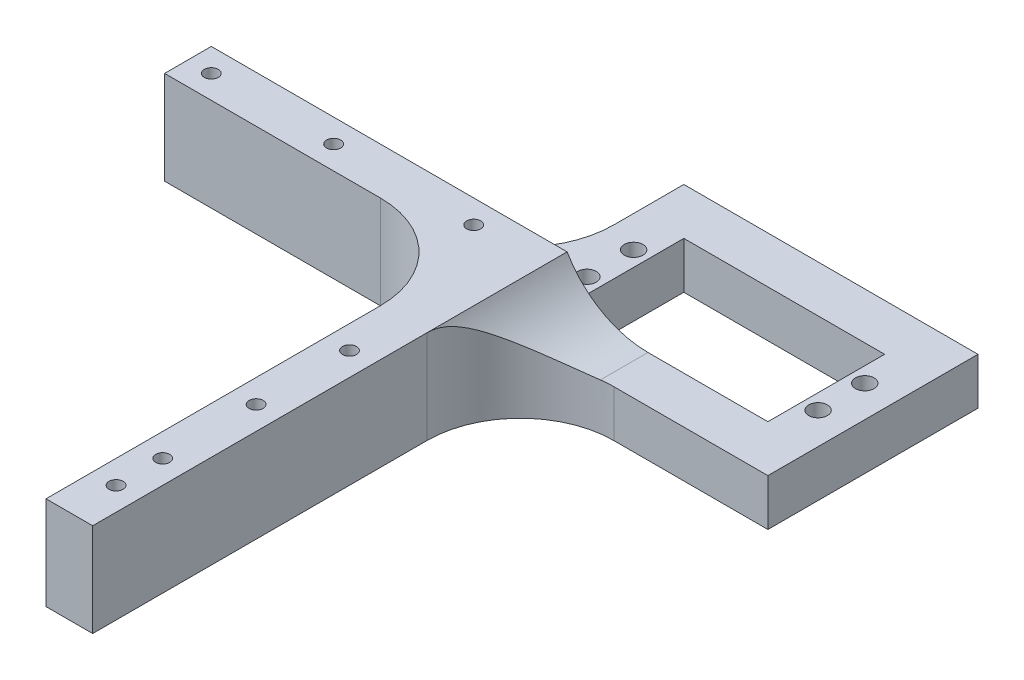
SolidWorks part; units mm, degrees
ref_plane "Front" through (0, 0, 0) normal (0, 0, 1) x (1, 0, 0)
ref_plane "Top" through (0, 0, 0) normal (0, 1, 0) x (1, 0, 0)
ref_plane "Right" through (0, 0, 0) normal (1, 0, 0) x (0, 0, -1)
sketch "Sketch1" plane through (0, 0, 0) normal (0, 1, 0) x (1, 0, 0)
  line L0 (0, 5) -> (0, -5)
  line L1 (-21.5, 12.5) -> (21.5, 12.5)
  line L2 (-21.5, 12.5) -> (-21.5, -12.5)
  line L3 (-21.5, -12.5) -> (21.5, -12.5)
  line L4 (21.5, 12.5) -> (21.5, -12.5)
  line L5 (-21.5, 12.5) -> (21.5, -12.5) construction
  line L6 (-21.5, -12.5) -> (21.5, 12.5) construction
  line L7 (-31.5, 22.5) -> (31.5, 22.5)
  line L8 (-31.5, 22.5) -> (-31.5, -22.5)
  line L9 (-31.5, -22.5) -> (31.5, -22.5)
  line L10 (31.5, 22.5) -> (31.5, -22.5)
  line L11 (-31.5, 22.5) -> (31.5, -22.5) construction
  line L12 (-31.5, -22.5) -> (31.5, 22.5) construction
  line L13 (-24.75, 5) -> (24.75, 5)
  line L14 (-24.75, -5) -> (24.75, -5)
  circle A0 centre (-24.75, 5) radius 2
  circle A1 centre (-24.75, -5) radius 2
  circle A2 centre (24.75, 5) radius 2
  circle A3 centre (24.75, -5) radius 2
  point P0 (0, 0)
  point P6 (0, 0)
  point P14 (0, 0)
  point P17 (0, 5)
  point P20 (0, -5)
  dimension "D1" = 43
  dimension "D2" = 25
  dimension "D3" = 10
  dimension "D4" = 10
  dimension "D5" = 10
  dimension "D6" = 49.5
extrude "Boss-Extrude1" add sketch "Sketch1" along normal blind 10 contours L10 L7 L8 L9 A3 L4 L3 L2 A1 A0 L1 A2 region at (0, 0, -21.7258)
sketch "Sketch2" plane through (-31.5, 0, 0) normal (-1, 0, 0) x (0, 0, 1)
  line L0 (-22.5, 0) -> (22.5, 0) construction
  line L1 (22.5, 10) -> (12.5, 10)
  line L3 (22.5, 0) -> (12.5, 0)
  line L5 (12.5, 0) -> (12.5, 20)
  line L6 (12.5, 20) -> (22.5, 20)
  line L7 (22.5, 10) -> (22.5, 0) construction
  line L8 (22.5, 20) -> (22.5, 0)
  line M3 (-22.5, 0) -> (22.5, 0)
  line M4 (22.5, 0) -> (22.5, 10)
  line M5 (22.5, 10) -> (-22.5, 10)
  dimension "D1" = 10
  dimension "D2" = 10
  dimension "D3" = 20
extrude "Boss-Extrude2" add sketch "Sketch2" along normal blind 76.2 contours L6 L5 M3 M4 | L8 L6 L5 M5 region at (-31.5, 5, 17.5) region at (-31.5, 15, 17.5)
sketch "Sketch3" plane through (0, 0, 22.5) normal (0, 0, 1) x (1, 0, 0)
  line L0 (-107.7, 0) -> (31.5, 0) construction
  line L1 (-21.5, 10) -> (-31.5, 10)
  line L2 (-21.5, 10) -> (-21.5, 0)
  line L3 (-21.5, 0) -> (-31.5, 0)
  line L4 (-31.5, 10) -> (-31.5, 0)
  line L5 (-107.7, 0) -> (-107.7, 20) construction
  point P7 (0, 0)
  dimension "D1" = 10
  dimension "D2" = 76.2
  dimension "D3" = 10
extrude "Boss-Extrude3" add sketch "Sketch3" along normal blind 91.6
sketch "Sketch5" plane through (0, 10, 0) normal (0, 1, 0) x (1, 0, 0)
  line L0 (-31.5, -12.5) -> (-21.5, -12.5)
  line L1 (-21.5, -12.5) -> (-21.5, -114.1)
  line L2 (-21.5, -114.1) -> (-31.5, -114.1)
  line L3 (-31.5, -114.1) -> (-31.5, -12.5)
extrude "Boss-Extrude4" add sketch "Sketch5" along normal blind 10
sketch "Sketch4" plane through (0, 10, 0) normal (0, 1, 0) x (1, 0, 0)
  line L0 (-107.7, -17.5) -> (-66.5, -17.5)
  line L1 (-107.7, -22.5) -> (-107.7, -12.5) construction
  line L2 (-66.5, -17.5) -> (-36.5, -17.5)
  circle A0 centre (-92.7, -17.5) radius 1.5
  circle A1 centre (-66.5, -17.5) radius 1.5
  circle A2 centre (-36.5, -17.5) radius 1.5
  dimension "D1" = 41.2
  dimension "D2" = 30
  dimension "D3" = 15
extrude "Cut-Extrude1" cut sketch "Sketch4" against normal through all and the other way through all contours L0 A0 | L0 A0 | A1 | A2 region at (-92.7, 10, 16.8634) region at (-92.7, 10, 18.1366)
fillet "Fillet5" radius 20 2 edges at (-31.5, 5, 12.5) (-31.5, 10, 22.5)
fillet "Fillet7" radius 20 1 edges at (-21.5, 10, 17.5)
fillet "Fillet8" radius 3 1 edges at (-36.5, 10, 12.5)
fillet "Fillet9" radius 20 1 edges at (-21.5, 10, 22.5)
sketch "Sketch6" plane through (-107.7, 0, 0) normal (-1, 0, 0) x (0, 0, 1)
  line L1 (12.5, 0) -> (22.5, 0)
  line L2 (12.5, 0) -> (12.5, 20)
  line L3 (12.5, 20) -> (22.5, 20)
  line L4 (22.5, 0) -> (22.5, 20)
extrude "Cut-Extrude2" cut sketch "Sketch6" against normal blind 10
sketch "Sketch7" plane through (0, 0, 0) normal (0, -1, 0) x (-1, 0, 0)
  line L0 (26.5, -114.1) -> (26.5, -94.1)
  line L1 (31.5, -114.1) -> (21.5, -114.1) construction
  line L2 (26.5, -94.1) -> (26.5, -54.1)
  circle A0 centre (26.5, -54.1) radius 1.5
  circle A1 centre (26.5, -94.1) radius 1.5
  circle A2 centre (26.5, -74.1) radius 1.5
  circle A3 centre (26.5, -104.1) radius 1.5
  dimension "D1" = 20
  dimension "D2" = 40
extrude "Cut-Extrude3" cut sketch "Sketch7" against normal through all contours A1 | A0 | A3 | A2
